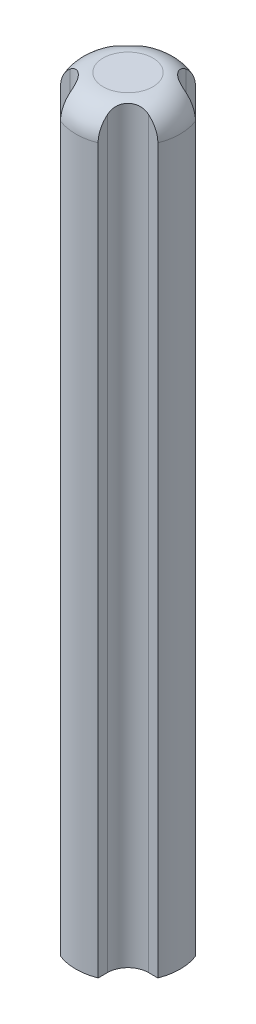
SolidWorks part; units mm, degrees
ref_plane "Front Plane" through (0, 0, 0) normal (0, 0, 1) x (1, 0, 0)
ref_plane "Top Plane" through (0, 0, 0) normal (0, 1, 0) x (1, 0, 0)
ref_plane "Right Plane" through (0, 0, 0) normal (1, 0, 0) x (0, 0, -1)
sketch "Sketch1" plane through (0, 0, 0) normal (0, 1, 0) x (1, 0, 0)
  circle A0 centre (0, 0) radius 3.825
  dimension "D1" = 7.65
extrude "Boss-Extrude1" add sketch "Sketch1" along normal blind 55
fillet "Fillet1" radius 2 1 edges at (0, 55, 3.825)
sketch "Sketch2" plane through (0, 55, 0) normal (0, 1, 0) x (1, 0, 0)
  line L0 (0, 0) -> (1.3789, -1.3789) construction
  line L1 (1.3789, -1.3789) -> (0, -1.3789) construction
  line L2 (1.3789, -1.3789) -> (3.8789, -1.3789)
  line L3 (1.3789, -1.3789) -> (1.3789, -3.8789)
  line L4 (1.3789, -3.8789) -> (3.8789, -3.8789)
  line L5 (3.8789, -1.3789) -> (3.8789, -3.8789)
  line L6 (0, -1.3789) -> (0, 0) construction
  dimension "D1" = 1.95
  dimension "D2" = 2.5
extrude "Cut-Extrude1" cut sketch "Sketch2" against normal through all
pattern_circular "CirPattern1" count 4 over 360 about axis through (0, 55, 0) along (0, 1, 0) of "Cut-Extrude1"
fillet "Fillet2" radius 1.5 4 edges at (1.3789, 27.498, -1.3789) (-1.3789, 27.498, -1.3789) (-1.3789, 27.498, 1.3789) (1.3789, 27.498, 1.3789)
